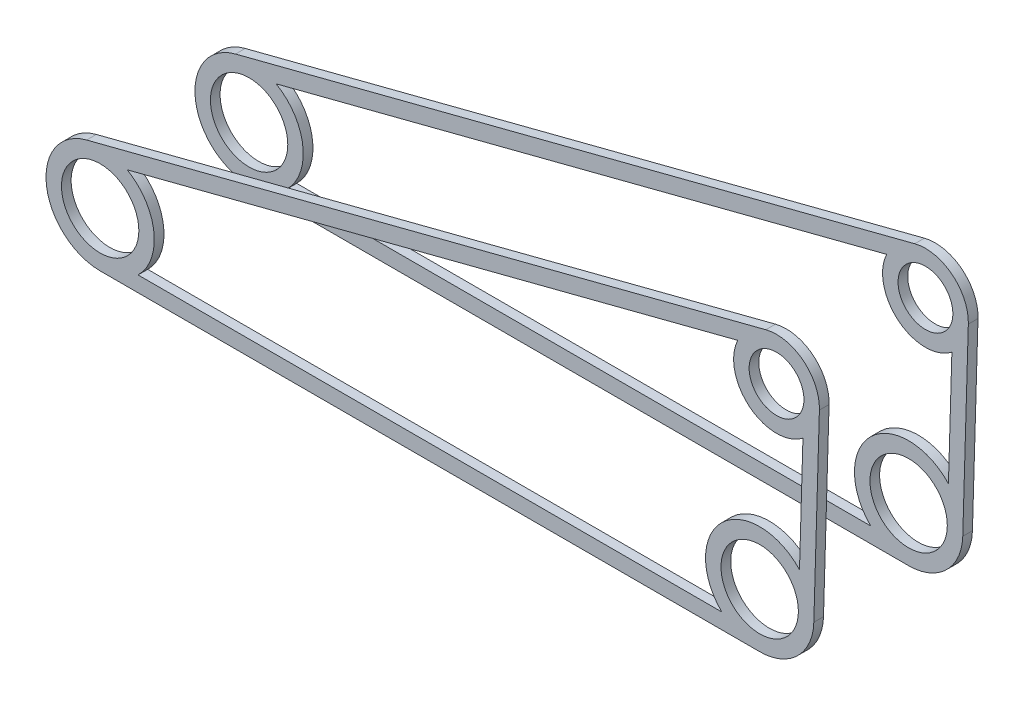
SolidWorks part; units mm, degrees
material "AISI 4130 Steel, annealed at 865C"
ref_plane "Front Plane" through (0, 0, 0) normal (0, 0, 1) x (1, 0, 0)
ref_plane "Top Plane" through (0, 0, 0) normal (0, 1, 0) x (1, 0, 0)
ref_plane "Right Plane" through (0, 0, 0) normal (1, 0, 0) x (0, 0, -1)
sketch "Sketch1" plane through (0, 0, 0) normal (0, 0, 1) x (1, 0, 0)
  line L0 (0, 0) -> (108.2624, 0) construction
  line L1 (108.2624, 0) -> (111.0253, 30.5662) construction
  line L2 (111.0253, 30.5662) -> (0, 0) construction
  line L3 (-2.2217, 8.6079) -> (109.2659, 37.3828)
  line L4 (118.0621, 30.3562) -> (117.1485, -0.2651)
  line L5 (108.2624, -8.89) -> (0, -8.89)
  line L6 (-1.5869, 6.1485) -> (109.9007, 34.9234)
  line L7 (0, -6.35) -> (108.2624, -6.35)
  line L8 (114.6096, -0.1894) -> (115.5233, 30.432)
  circle A0 centre (0, 0) radius 6.35
  circle A1 centre (108.2624, 0) radius 6.35
  circle A2 centre (111.0253, 30.5662) radius 4.5
  circle A3 centre (0, 0) radius 8.89
  circle A4 centre (108.2624, 0) radius 8.89
  circle A5 centre (111.0253, 30.5662) radius 7.04
  dimension "D1" = 9
  dimension "D2" = 12.7
  dimension "D3" = 12.7
  dimension "D6" = 2.54
  dimension "D7" = 2.54
  dimension "D8" = 2.54
  dimension "D4" = 108.2624
  dimension "D5" = 30.6908
  dimension "D9" = 115.156
extrude "Boss-Extrude1" add sketch "Sketch1" along normal blind 1.5875 from offset 11.43 contours A5 L3 A3 L6 | L6 A3 L7 A0 | A4 L7 A3 L5 | L7 A4 L8 A1 | A5 L8 A4 L4 | A5 L6 A2 L8 | L7 A3 L6 A0 | L8 A4 L7 A1 | L6 A5 L8 A2 region at (1.1652, 8.5779, 0) region at (54.0841, 21.8473, 0) region at (115.224, 35.9862, 0) region at (54.1312, -7.6407, 0) region at (7.545, 4.3611, 0) region at (107.3201, 34.0899, 0) region at (104.9826, -8.0339, 0) region at (116.4282, 15.329, 0) region at (102.2217, 6.2236, 0)
extrude "Boss-Extrude2" add sketch "Sketch1<4>" against normal blind 1.5875 from offset 11.43 separate body contours A5 L3 A3 L6 | L6 A3 L7 A0 | L7 A3 L6 A0 | A4 L7 A3 L5 | L7 A4 L8 A1 | L8 A4 L7 A1 | A5 L8 A4 L4 | L6 A5 L8 A2 | A5 L6 A2 L8 region at (1.1652, 8.5779, 0) region at (54.0841, 21.8473, 0) region at (115.224, 35.9862, 0) region at (54.1312, -7.6407, 0) region at (7.545, 4.3611, 0) region at (107.3201, 34.0899, 0) region at (104.9826, -8.0339, 0) region at (116.4282, 15.329, 0) region at (102.2217, 6.2236, 0) offset against normal yes
sketch "Sketch1<4>" plane through (0, 0, 0) normal (0, 0, 1) x (1, 0, 0) same geometry as "Sketch1"
equation "\"D19@Boss-Extrude2\"=.45"
